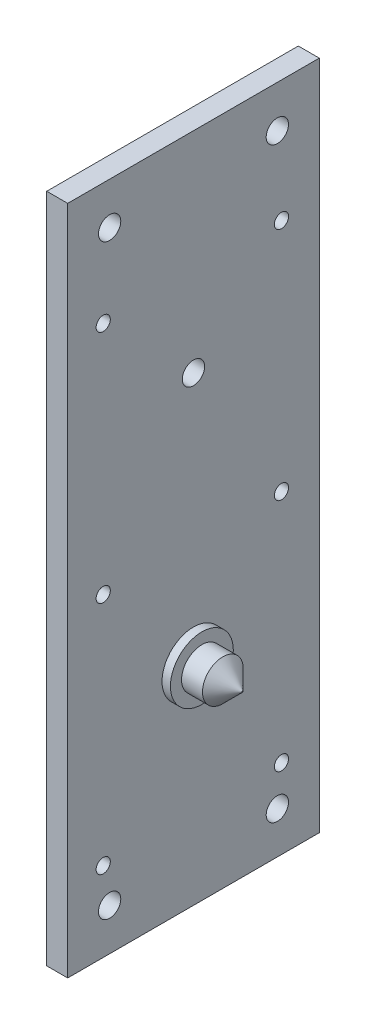
SolidWorks part; units mm, degrees
ref_plane "Front Plane" through (0, 0, 0) normal (0, 0, 1) x (1, 0, 0)
ref_plane "Top Plane" through (0, 0, 0) normal (0, 1, 0) x (1, 0, 0)
ref_plane "Right Plane" through (0, 0, 0) normal (1, 0, 0) x (0, 0, -1)
sketch "Sketch1" plane through (0, 0, 0) normal (1, 0, 0) x (0, 0, -1)
  line L5 (0, 76.2) -> (0, 0) construction
  line L6 (-38.1, -63.5) -> (38.1, -63.5)
  line L7 (-38.1, -63.5) -> (-38.1, 139.7)
  line L8 (-38.1, 139.7) -> (38.1, 139.7)
  line L9 (38.1, -63.5) -> (38.1, 139.7)
  line L10 (-38.1, -63.5) -> (38.1, 139.7) construction
  line L11 (-38.1, 139.7) -> (38.1, -63.5) construction
  arc A0 (0, -34.925) -> (33.7761, 8.8845) centre (0, 0) ccw construction
  arc A1 (12.2967, 79.375) -> (-12.2967, 79.375) centre (0, 76.2) ccw construction
  arc A2 (33.7761, 8.8845) -> (-33.8552, 8.5779) centre (0, 0) ccw construction
  arc A3 (-12.2967, 79.375) -> (12.2967, 79.375) centre (0, 76.2) ccw construction
  circle A4 centre (0, 76.2) radius 4.7625 construction
  circle A5 centre (0, 0) radius 6.35 construction
  arc A6 (-33.8552, 8.5779) -> (0, -34.925) centre (0, 0) ccw construction
  point P10 (0, 38.1)
  dimension "D1" = 69.85
  dimension "D2" = 25.4
  dimension "D4" = 9.525
  dimension "D5" = 12.7
  dimension "D6" = 76.2
  dimension "D3" = 139.7
  dimension "D7" = 203.2
  dimension "D8" = 63.5
extrude "Boss-Extrude1" add sketch "Sketch1" along normal blind 6.35
sketch "Sketch6" plane through (6.35, 0, 0) normal (1, 0, 0) x (0, 0, -1)
  circle A0 centre (0, 0) radius 9.525
  dimension "D1" = 19.05
extrude "Boss-Extrude4" add sketch "Sketch6" along normal blind 2.54
sketch "Sketch5" plane through (8.89, 0, 0) normal (1, 0, 0) x (0, 0, -1)
  circle A0 centre (0, 0) radius 6.1595
  dimension "D1" = 12.319
extrude "Boss-Extrude3" add sketch "Sketch5" along normal blind 12.319
sketch "Sketch3" [suppressed] plane through (0, 22.225, 0) normal (0, -1, 0) x (1, 0, 0)
  line L0 (6.35, 6.5515) -> (6.35, -6.1485) construction
  line L6 (12.7, 6.5515) -> (12.7, -6.1485) construction
  line L7 (17.78, -6.1485) -> (6.35, -6.1485) construction
  circle A0 centre (12.7, 0.2015) radius 3.175
  point P12 (12.7, 0.2015)
  dimension "D1" = 6.35
  dimension "D2" = 6.35
extrude "Cut-Extrude1" [suppressed] cut sketch "Sketch3" against normal through all
sketch "Sketch4" [suppressed] plane through (17.78, 0, 0) normal (1, 0, 0) x (0, 0, -1)
  line L0 (-6.5515, 45.72) -> (6.1485, 45.72) construction
  line L3 (-0.2015, 50.165) -> (-0.2015, 41.275) construction
  line L4 (2.9735, 50.165) -> (2.9735, 41.275)
  line L5 (-3.3765, 50.165) -> (-3.3765, 41.275)
  line L8 (6.1485, 22.225) -> (6.1485, 66.675) construction
  arc A0 (2.9735, 50.165) -> (-3.3765, 50.165) centre (-0.2015, 50.165) ccw
  arc A1 (-3.3765, 41.275) -> (2.9735, 41.275) centre (-0.2015, 41.275) ccw
  circle A2 centre (-0.2015, 60.325) radius 3.175
  point P5 (-0.2015, 45.72)
  point P8 (-0.2015, 45.72)
  dimension "D4" = 6.35
  dimension "D1" = 41.275
  dimension "D2" = 6.35
  dimension "D3" = 8.89
  dimension "D5" = 19.05
extrude "Cut-Extrude2" [suppressed] cut sketch "Sketch4" against normal through all
chamfer "Chamfer1" distance 5.969 angle 45 1 edges at (21.209, 0, -6.1595)
hole_wizard "1/4 Clearance Hole1" positions "Sketch10" profile "Sketch11" hole size "1/4" standard "ANSI Inch" end condition through all
sketch "Sketch10" plane through (6.35, 0, 0) normal (1, 0, 0) x (0, 0, -1)
  line L1 (-38.1, -63.5) -> (38.1, -63.5) construction
  line L2 (-38.1, 139.7) -> (-38.1, -63.5) construction
  line L3 (-38.1, -50.8) -> (38.1, -50.8) construction
  line L4 (38.1, -63.5) -> (38.1, 139.7) construction
  line L6 (0, -50.8) -> (0, 139.7) construction
  line L7 (38.1, 139.7) -> (-38.1, 139.7) construction
  line L8 (25.4, 127) -> (-25.4, 127) construction
  point P0 (0, 76.2)
  point P3 (25.4, -50.8)
  point P6 (-25.4, -50.8)
  point P29 (-25.4, 127)
  point P31 (25.4, 127)
  dimension "D1" = 12.7
  dimension "D2" = 12.7
  dimension "D3" = 63.5
  dimension "D4" = 139.7
  dimension "D5" = 190.5
sketch "Sketch11" plane through (6.35, 76.2, 0) normal (0, 1, 0) x (0, 0, -1)
  line L0 (0, 0) -> (0, 6.35)
  line L1 (0, 6.35) -> (3.3782, 6.35)
  line L2 (3.3782, 6.35) -> (3.3782, 0)
  line L5 (3.3782, 0) -> (0, 0)
  line L11 (0, -6.35) -> (0, 107.95) construction
  dimension "Thru Hole Dia." = 6.7564
  dimension "Thru Hole Depth" = 6.35
sketch "Sketch12" plane through (0, 0, 0) normal (-1, 0, 0) x (0, 0, 1)
  circle A0 centre (-26.6465, -39.4028) radius 2.15 construction
  circle A1 centre (-26.6465, 31.7172) radius 2.15 construction
  circle A2 centre (-26.6465, 102.8372) radius 2.15 construction
  circle A3 centre (27.342, 102.8372) radius 2.15 construction
  circle A4 centre (27.342, 31.7172) radius 2.15 construction
  circle A5 centre (27.342, -39.4028) radius 2.15 construction
  circle A6 centre (-26.6465, -39.4028) radius 2.15
  circle A7 centre (-26.6465, 31.7172) radius 2.15
  circle A8 centre (-26.6465, 102.8372) radius 2.15
  circle A9 centre (27.342, 102.8372) radius 2.15
  circle A10 centre (27.342, 31.7172) radius 2.15
  circle A11 centre (27.342, -39.4028) radius 2.15
extrude "Cut-Extrude3" cut sketch "Sketch12" against normal blind 6.35
